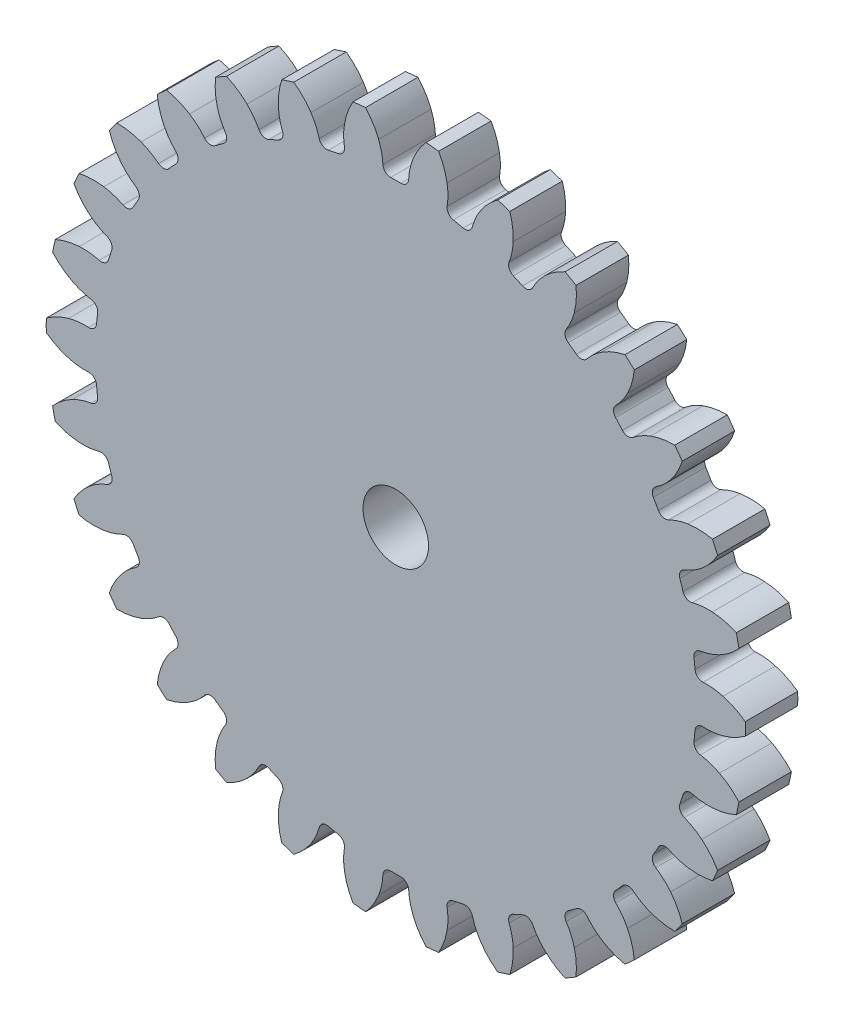
SolidWorks part; units mm, degrees
ref_plane "Front Plane" through (0, 0, 0) normal (0, 0, 1) x (1, 0, 0)
ref_plane "Top Plane" through (0, 0, 0) normal (0, 1, 0) x (1, 0, 0)
ref_plane "Right Plane" through (0, 0, 0) normal (1, 0, 0) x (0, 0, -1)
sketch "Sketch1" plane through (0, 0, 0) normal (0, 0, 1) x (1, 0, 0)
  line L0 (0, 0) -> (47.625, 0) construction
  line L1 (47.625, 0) -> (50.8, 0) construction
  circle A0 centre (0, 0) radius 50.8
  circle A1 centre (0, 0) radius 47.625 construction
  dimension "D2" = 95.25
  dimension "D1" = 3.175
extrude "GEAR_BASE" add sketch "Sketch1" along normal mid plane 7.62
sketch "Sketch2" plane through (0, 0, 3.81) normal (0, 0, 1) x (1, 0, 0)
  line L0 (0, 0) -> (43.6562, 0) construction
  line L1 (43.6562, 0) -> (47.625, 0) construction
  line L2 (0, 0) -> (-50.8, 0) construction
  line L3 (0, 0) -> (-47.5597, -2.494) construction
  line L4 (-47.5597, -2.494) -> (-48.4854, 15.1594) construction
  line L5 (0, 0) -> (-49.6899, -10.5619) construction
  line L6 (-47.5597, -2.494) -> (-43.5589, -2.9143) construction
  line L7 (-47.0389, -7.4487) -> (-43.2129, -6.2057) construction
  line L8 (0, 0) -> (-47.0389, -7.4487) construction
  line L9 (-47.5597, -2.494) -> (-50.7917, -0.9177) construction
  line L10 (-47.0389, -7.4487) -> (-49.8726, -9.6625) construction
  line L11 (-47.0389, -7.4487) -> (-46.5204, -9.8882) construction
  line L12 (-47.0389, -7.4487) -> (-44.274, -24.9088) construction
  line L13 (-47.5597, -2.494) -> (-47.5597, 0) construction
  circle A0 centre (0, 0) radius 47.625 construction
  circle A1 centre (0, 0) radius 43.6562 construction
  circle A2 centre (0, 0) radius 50.8 construction
  arc A3 (-49.8726, -9.6625) -> (-50.7917, -0.9177) centre (0, 0) cw
  arc A4 (-43.4883, -3.8254) -> (-44.6549, -2.8132) centre (-44.5953, -3.9228) ccw
  arc A5 (-44.264, -6.5326) -> (-43.3334, -5.2999) centre (-44.4364, -5.4348) ccw
  arc A6 (-43.3334, -5.2999) -> (-43.4883, -3.8254) centre (0, 0) cw
  arc A7 (-49.8726, -9.6625) -> (-47.0389, -7.4487) centre (-42.4148, -16.2882) cw
  arc A8 (-50.7917, -0.9177) -> (-47.5597, -2.494) centre (-44.8744, 7.1137) ccw
  arc A9 (-47.0389, -7.4487) -> (-44.264, -6.5326) centre (-42.8676, -15.4226) cw
  arc A10 (-47.5597, -2.494) -> (-44.6549, -2.8132) centre (-45.1374, 6.173) ccw
  dimension "D1" = 95.25
  dimension "D11" = 1.1112
  dimension "D12" = 9.9758
  dimension "D2" = 3.9688
  dimension "D3" = 12
  dimension "D5" = 9
  dimension "D7" = 9
  dimension "D8" = 4.9821
  dimension "D9" = 20
  dimension "D10" = 20
  dimension "D6" = 2.494
  dimension "D4" = 2.494
extrude "GEAR_CUT" cut sketch "Sketch2" against normal through all
ref_axis "GEAR_AXIS" through (0, 0, -3.2131) along (0, 0, 1)
pattern_circular "GEAR_TEETH" count 30 over 360 about axis through (0, 0, -3.2131) along (0, 0, 1) of "GEAR_CUT"
sketch "Sketch3" plane through (0, 0, 3.81) normal (0, 0, 1) x (1, 0, 0)
  circle A0 centre (0, 0) radius 4.7625
  dimension "D1" = 9.525
extrude "BORE" cut sketch "Sketch3" against normal through all
equation "\"N_teeth\" = 30"
equation "\"pitch_diameter\"= \"N_teeth\" / \"Pitch\""
equation "\"Pitch\" = 8"
equation "\"addendum\"=1.000/\"Pitch\""
equation "\"face_width\"=0.23"
equation "\"deddendum\"=1.250/\"Pitch\""
equation "\"tooth_thickness\"=1.571/\"Pitch\""
equation "\"Pressure_Angle\"=20.000000"
equation "\"base_fillet\"=0.35/\"Pitch\""
equation "\"D1@Sketch1\"=\"addendum\""
equation "\"D2@Sketch1\"=\"pitch_diameter\""
equation "\"D1@GEAR_BASE\"=\"GMaterial\""
equation "\"D1@Sketch2\"= \"pitch_diameter\""
equation "\"D2@Sketch2\"=\"deddendum\""
equation "\"D4@Sketch2\"=\"tooth_thickness\"/2"
equation "\"D6@Sketch2\"=\"tooth_thickness\"/2"
equation "\"D9@Sketch2\"=\"Pressure_Angle\""
equation "\"D10@Sketch2\"=\"Pressure_Angle\""
equation "\"D11@Sketch2\"=\"base_fillet\""
equation "\"D12@Sketch2\"=2*\"tooth_thickness\""
equation "\"D3@Sketch2\" = 360 / \"N_teeth\""
equation "\"D1@GEAR_TEETH\" = \"N_teeth\""
equation "\"MDF\"= .3"
equation "\"Foamcore\"= .1"
equation "\"GMaterial\"= .3"
